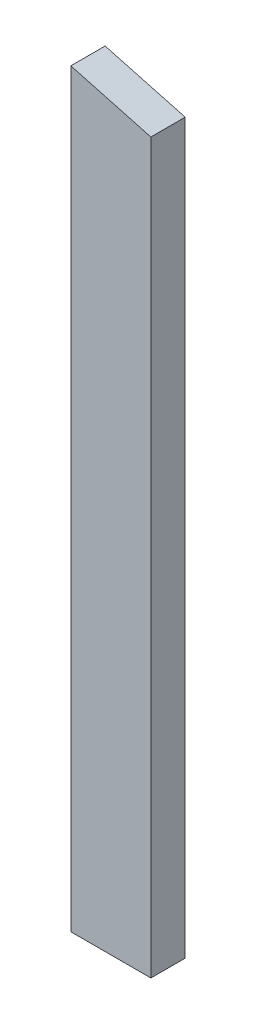
SolidWorks part; units mm, degrees
material "Pine"
ref_plane "Front Plane" through (0, 0, 0) normal (0, 0, 1) x (1, 0, 0)
ref_plane "Top Plane" through (0, 0, 0) normal (0, 1, 0) x (1, 0, 0)
ref_plane "Right Plane" through (0, 0, 0) normal (1, 0, 0) x (0, 0, -1)
sketch "Sketch1" plane through (0, 0, 0) normal (0, 0, 1) x (1, 0, 0)
  line L0 (-108.5345, -3.9032) -> (-108.5345, 1464.0363)
  line L1 (-248.0476, -3.9032) -> (-248.0476, 826.5024)
  line L2 (-870.5345, -3.9032) -> (-870.5345, 625.8363)
  line L3 (-972.1345, 737.9573) -> (-972.1345, 834.2968)
  line L4 (-768.9345, 834.2968) -> (-768.9345, 986.6968)
  line L5 (-972.1345, 834.2968) -> (-768.9345, 834.2968)
  line L6 (-528.0858, 1843.9468) -> (-737.1845, 1843.9468)
  line L7 (-968.4148, 728.977) -> (-874.2542, 634.8165)
  line L8 (-737.1845, 1672.0154) -> (-737.1845, 1762.6932)
  line L9 (-520.195, 1875.6968) -> (-756.2345, 1875.6968)
  line L10 (-112.2542, 1473.0165) -> (-511.2148, 1871.977)
  line L11 (-737.1845, 1692.941) -> (-241.631, 1467.6894)
  line L12 (-596.8655, 1608.234) -> (-737.1845, 983.1768)
  line L13 (-763.9746, 985.3593) -> (-203.7845, 834.2968)
  line L14 (-761.4898, 1669.1128) -> (-638.6318, 1613.2683)
  line L15 (-631.4955, 1598.9249) -> (-768.9345, 986.6968)
  line L16 (-768.9345, 1680.6745) -> (-768.9345, 1862.9968)
  line L17 (-737.1845, 1780.4468) -> (-737.1845, 1843.9468)
  line L18 (-737.1845, 1692.941) -> (-737.1845, 1843.9468) construction
  line L19 (-737.1845, 1692.941) -> (-737.1845, 1762.6932) construction
  line L20 (-838.7845, -3.9032) -> (-838.7845, 834.2968)
  line L21 (-745.0674, 1675.5986) -> (-249.5139, 1450.347) construction
  line L22 (-140.2845, -3.9032) -> (-140.2845, 1456.1455)
  line L23 (-140.2845, 1456.1455) -> (-528.0858, 1843.9468)
  line L24 (-537.8111, 1581.3911) -> (-673.6845, 976.1369)
  line L25 (-768.9345, 966.9663) -> (-203.7845, 814.5663)
  line L26 (-737.1845, 1672.0154) -> (-203.7845, 1429.5608)
  line L27 (-528.0858, 1843.9468) -> (-554.3883, 1780.4468)
  line L28 (-140.2845, 1456.1455) -> (-203.7845, 1429.8429)
  line L29 (-775.2845, -3.9032) -> (-775.2845, 834.2968)
  line L30 (-773.8944, 968.3038) -> (-208.7444, 815.9038) construction
  line L31 (-203.7845, -3.9032) -> (-203.7845, 1429.8429)
  line L32 (-203.7845, 1429.8429) -> (-554.3883, 1780.4468)
  line L33 (-554.3883, 1780.4468) -> (-737.1845, 1780.4468)
  line L34 (-768.9345, 966.9663) -> (-763.9746, 985.3593)
  line L35 (-737.1845, 1762.6932) -> (-369.5099, 1595.5683)
  line L36 (-673.6845, 1733.8295) -> (-599.2171, 1699.9807) construction
  line L37 (-737.1845, 1692.941) -> (-625.4936, 1642.1724) construction
  line L38 (-538.5586, 1578.0615) -> (-673.6845, 976.1369) construction
  line L39 (-600.5166, 1591.9704) -> (-737.1845, 983.1768) construction
  line L40 (-554.3883, 1780.4468) -> (-673.6845, 1780.4468) construction
  line L41 (-203.7845, 91.3468) -> (-203.7845, 1429.8429) construction
  line L42 (-140.2845, 27.8468) -> (-140.2845, 1456.1455) construction
  line L43 (-775.2845, 91.3468) -> (-775.2845, 625.8363) construction
  line L44 (-838.7845, 27.8468) -> (-838.7845, 625.8363) construction
  line L45 (-203.7845, 91.3468) -> (-775.2845, 91.3468) construction
  line L46 (-140.2845, 27.8468) -> (-838.7845, 27.8468) construction
  line L47 (-940.3845, 745.8481) -> (-851.8036, 657.2672) construction
  line L48 (-843.7807, 739.0468) -> (-806.9023, 702.1685) construction
  line L49 (-843.7807, 739.0468) -> (-673.6845, 739.0468) construction
  line L50 (-940.3845, 802.5468) -> (-737.1845, 802.5468) construction
  line L51 (-940.3845, 745.8481) -> (-940.3845, 802.5468) construction
  line L52 (-843.7807, 739.0468) -> (-843.7807, 739.0468) construction
  line L53 (-673.6845, 1733.8295) -> (-673.6845, 1780.4468) construction
  line L54 (-756.2345, 1692.941) -> (-756.2345, 1792.2779) construction
  line L55 (-756.2345, 1792.2779) -> (-361.627, 1612.9108) construction
  line L56 (-673.6845, 739.0468) -> (-673.6845, 976.1369) construction
  line L57 (-737.1845, 802.5468) -> (-737.1845, 983.1768) construction
  line L58 (-768.9345, 986.6968) -> (-203.7845, 834.2968) construction
  line L59 (-203.7845, 834.2968) -> (-208.7444, 815.9038)
  line L60 (-768.9345, 901.198) -> (-203.7845, 748.798)
  line L61 (-846.7775, 922.1894) -> (-163.9675, 738.0608) construction
  line L62 (-768.9345, 966.9663) -> (-208.7444, 815.9038) construction
  line L63 (-108.5345, -3.9032) -> (-248.0476, -3.9032)
  line L64 (-808.7515, 1063.2022) -> (-125.9415, 879.0737) construction
  line L65 (-125.9415, 879.0737) -> (-163.9675, 738.0608) construction
  line L66 (-846.7775, 922.1894) -> (-808.7515, 1063.2022) construction
  line L67 (-336.9476, -3.9032) -> (-336.9476, 850.4754)
  line L68 (-108.5345, -3.9032) -> (-870.5345, -3.9032) construction
  line L69 (-108.5345, -3.9032) -> (-870.5345, -3.9032)
  line L70 (-336.9476, -3.9032) -> (-336.9476, 760.7341) construction
  line L71 (-248.0476, -3.9032) -> (-248.0476, 760.7341) construction
  line L72 (-108.5345, 17.9898) -> (-870.5345, 17.9898)
  arc A0 (-108.5345, 1464.0363) -> (-112.2542, 1473.0165) centre (-121.2345, 1464.0363) ccw
  arc A1 (-511.2148, 1871.977) -> (-520.195, 1875.6968) centre (-520.195, 1862.9968) ccw
  arc A2 (-768.9345, 1862.9968) -> (-756.2345, 1875.6968) centre (-756.2345, 1862.9968) cw
  arc A3 (-768.9345, 1680.6745) -> (-761.4898, 1669.1128) centre (-756.2345, 1680.6745) ccw
  arc A4 (-631.4955, 1598.9249) -> (-638.6318, 1613.2683) centre (-643.8871, 1601.7067) ccw
  arc A5 (-972.1345, 737.9573) -> (-968.4148, 728.977) centre (-959.4345, 737.9573) ccw
  arc A6 (-870.5345, 625.8363) -> (-874.2542, 634.8165) centre (-883.2345, 625.8363) ccw
  arc A7 (-737.1845, 1843.9468) -> (-737.1845, 1843.9468) centre (-737.1845, 1843.9468) cw
  arc A8 (-737.1845, 1692.941) -> (-737.1845, 1692.941) centre (-737.1845, 1692.941) ccw
  arc A12 (-140.2845, 1456.1455) -> (-140.2845, 1456.1455) centre (-140.2845, 1456.1455) ccw
  arc A13 (-528.0858, 1843.9468) -> (-528.0858, 1843.9468) centre (-528.0858, 1843.9468) ccw
  arc A14 (-600.5166, 1591.9704) -> (-625.4936, 1642.1724) centre (-643.8871, 1601.7067) ccw construction
  arc A16 (-203.7845, 1429.8429) -> (-203.7845, 1429.8429) centre (-203.7845, 1429.8429) ccw
  arc A17 (-554.3883, 1780.4468) -> (-554.3883, 1780.4468) centre (-554.3883, 1780.4468) ccw
  arc A18 (-673.6845, 1780.4468) -> (-673.6845, 1780.4468) centre (-673.6845, 1780.4468) cw
  arc A19 (-673.6845, 1733.8295) -> (-673.6845, 1733.8295) centre (-673.6845, 1733.8295) ccw
  arc A20 (-838.7845, 625.8363) -> (-851.8036, 657.2672) centre (-883.2345, 625.8363) ccw construction
  arc A21 (-775.2845, 625.8363) -> (-806.9023, 702.1685) centre (-883.2345, 625.8363) ccw construction
  arc A22 (-843.7807, 739.0468) -> (-843.7807, 739.0468) centre (-843.7807, 739.0468) ccw construction
  arc A23 (-940.3845, 745.8481) -> (-940.3845, 745.8481) centre (-940.3845, 745.8481) ccw construction
  arc A24 (-756.2345, 1692.941) -> (-745.0674, 1675.5986) centre (-737.1845, 1692.941) ccw construction
  dimension "D1" = 12.7
  dimension "D7" = 88.9
  dimension "D2" = 31.75
  dimension "D3" = 63.5
  dimension "D4" = 19.05
  dimension "D5" = 19.05
  dimension "D6" = 63.5
  dimension "D8" = 21.893
extrude "Boss-Extrude1" add sketch "Sketch1" along normal blind 38.1 contours L69 L1 L60 L67 | L67 L60 L1 L25 region at (-292.7329, 395.387, 0) region at (-292.4976, 805.6048, 0)
